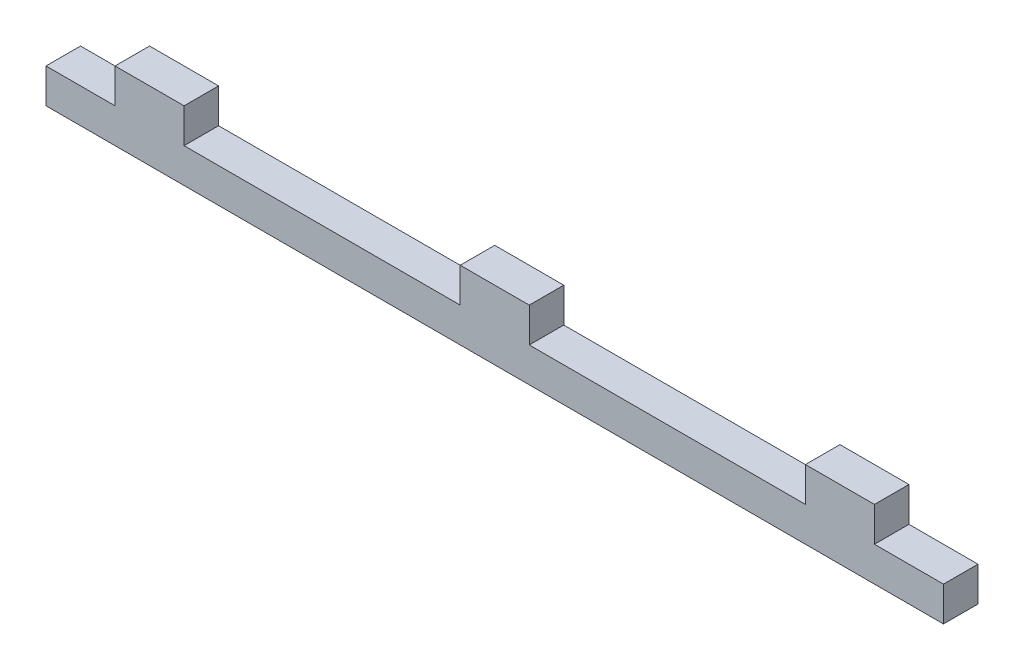
SolidWorks part; units mm, degrees
ref_plane "Front Plane" through (0, 0, 0) normal (0, 0, 1) x (1, 0, 0)
ref_plane "Top Plane" through (0, 0, 0) normal (0, 1, 0) x (1, 0, 0)
ref_plane "Right Plane" through (0, 0, 0) normal (1, 0, 0) x (0, 0, -1)
sketch "Sketch2" plane through (0, 0, 0) normal (0, 1, 0) x (1, 0, 0)
  line L0 (0, 0) -> (0, 6) construction
  dimension "D1" = 6
sketch "Sketch1" plane through (0, 0, 0) normal (0, 0, 1) x (1, 0, 0)
  line L0 (0, 0) -> (0, 9) construction
  line L1 (-78, -3) -> (78, -3)
  line L2 (-78, -3) -> (-78, 3)
  line L3 (-78, 3) -> (78, 3)
  line L4 (78, -3) -> (78, 3)
  line L5 (-78, -3) -> (78, 3) construction
  line L6 (-78, 3) -> (78, -3) construction
  line L7 (-66, 3) -> (-54, 3)
  line L8 (-66, 3) -> (-66, 9)
  line L9 (-66, 9) -> (-54, 9)
  line L10 (-54, 3) -> (-54, 9)
  line L11 (-6, 3) -> (6, 3)
  line L12 (-6, 3) -> (-6, 9)
  line L13 (-6, 9) -> (6, 9)
  line L14 (6, 3) -> (6, 9)
  line L15 (54, 3) -> (66, 3)
  line L16 (54, 3) -> (54, 9)
  line L17 (54, 9) -> (66, 9)
  line L18 (66, 3) -> (66, 9)
  line L19 (-54, 9) -> (-6, 9) construction
  line L20 (6, 9) -> (54, 9) construction
  point P0 (0, 0)
  dimension "D1" = 6
  dimension "D2" = 156
  dimension "D3" = 12
  dimension "D4" = 12
extrude "Boss-Extrude1" add sketch "Sketch1" against normal up to vertex (6 mm away) contours L3 L10 L9 L8 | L1 L4 L3 L2 | L3 L14 L13 L12 | L3 L18 L17 L16 region at (0, 0, 0) region at (-60, 6, 0) region at (60, 6, 0) region at (0, 6, 0) up to point (0, 0, -6)
equation "\"t_wood\"= 6' Thickness of the wood"
equation "\"t_glass\"= 2.5'Thickness of glass panels"
equation "\"w_glass\"= 181"
equation "\"h_glass\"= 151"
equation "\"h_food_internal\" = 60"
equation "\"entry_height\"= 20"
equation "\"entry diameter\"= 8"
equation "\"glass_bottom_overlap\"= 8"
equation "\"default_finger_size\"= 12"
equation "\"brood_depth\"= 42"
equation "\"outer_box_depth\" = \"brood_depth\" + ( 2 * \"t_glass\" ) + ( 2 * \"t_wood\" )"
equation "\"outer_box_width\"= \"w_glass\" + ( 2 * \"t_wood\" )"
equation "\"food_top_clearance\"= 10"
equation "\"outer_box_height\"= \"t_wood\" + \"h_glass\" + \"t_wood\" + \"h_food_internal\" + \"food_top_clearance\" + \"t_wood\""
equation "\"food_internal_depth\"= \"brood_depth\" + \"t_glass\" + \"t_glass\" - \"t_wood\" - \"t_wood\""
equation "\"food_channel_clearance_width\"= 14"
equation "\"bar_top_play\"= 0.5"
equation "\"bar_entry_angle\"= 10"
equation "\"bar_width\"= 20"
equation "\"entry_disk_play\"= 0.3"
equation "\"D1@Sketch2\"=\"t_wood\""
equation "\"D1@Sketch1\"=\"t_wood\""
equation "\"D2@Sketch1\"=\"w_glass\"-( \"t_wood\" *4)-1"
equation "\"D3@Sketch1\"=\"t_wood\"*2"
equation "\"D4@Sketch1\"=\"default_finger_size\""
